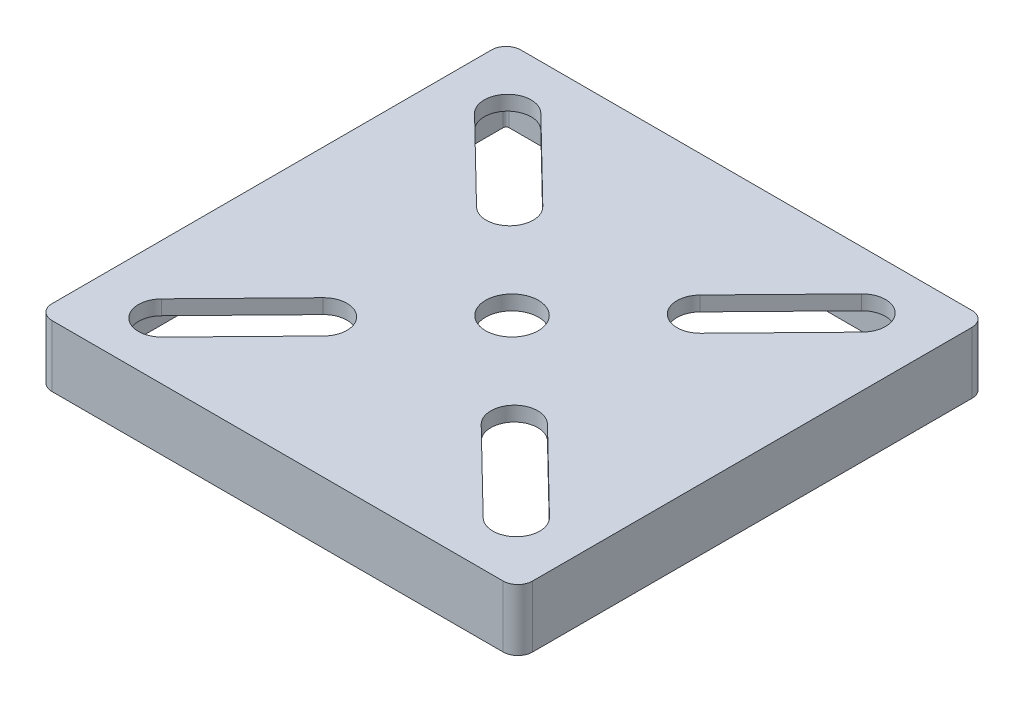
SolidWorks part; units mm, degrees
note: '?' marks a value the reader was unsure of. The reader was unsure of these and kept them because the rebuilt part matched: shared geometry of "Sketch1<4>".
ref_plane "Front Plane" through (0, 0, 0) normal (0, 0, 1) x (1, 0, 0)
ref_plane "Top Plane" through (0, 0, 0) normal (0, 1, 0) x (1, 0, 0)
ref_plane "Right Plane" through (0, 0, 0) normal (1, 0, 0) x (0, 0, -1)
sketch "Sketch1" plane through (0, 0, 0) normal (0, 1, 0) x (1, 0, 0)
  line L0 (0, 80) -> (0, -80) construction
  line L1 (-77, 80) -> (77, 80)
  line L2 (-82, 75) -> (-82, -75)
  line L3 (-77, -80) -> (77, -80)
  line L4 (82, 75) -> (82, -75)
  line L5 (-82, 80) -> (0, 0) construction
  line L6 (-54.8892, 64.727) -> (-26.9737, 37.4924)
  line L7 (-66.0624, 53.2745) -> (-38.1469, 26.0399)
  line L8 (-66.0624, 53.2745) -> (-54.8892, 64.727) construction
  line L9 (-38.1469, 26.0399) -> (-26.9737, 37.4924) construction
  line L10 (64.727, 54.8892) -> (37.4924, 26.9737)
  line L11 (53.2745, 66.0624) -> (26.0399, 38.1469)
  line L12 (54.8892, -64.727) -> (26.9737, -37.4924)
  line L13 (66.0624, -53.2745) -> (38.1469, -26.0399)
  line L14 (-64.727, -54.8892) -> (-37.4924, -26.9737)
  line L15 (-53.2745, -66.0624) -> (-26.0399, -38.1469)
  circle A0 centre (0, 0) radius 9
  arc A1 (-66.0624, 53.2745) -> (-54.8892, 64.727) centre (-60.4758, 59.0008) cw
  arc A2 (-26.9737, 37.4924) -> (-38.1469, 26.0399) centre (-32.5603, 31.7661) cw
  arc A3 (82, -75) -> (77, -80) centre (77, -75) cw
  arc A4 (-82, -75) -> (-77, -80) centre (-77, -75) ccw
  arc A5 (82, 75) -> (77, 80) centre (77, 75) ccw
  arc A6 (-82, 75) -> (-77, 80) centre (-77, 75) cw
  arc A7 (37.4924, 26.9737) -> (26.0399, 38.1469) centre (31.7661, 32.5603) cw
  arc A8 (53.2745, 66.0624) -> (64.727, 54.8892) centre (59.0008, 60.4758) cw
  arc A9 (26.9737, -37.4924) -> (38.1469, -26.0399) centre (32.5603, -31.7661) cw
  arc A10 (66.0624, -53.2745) -> (54.8892, -64.727) centre (60.4758, -59.0008) cw
  arc A11 (-37.4924, -26.9737) -> (-26.0399, -38.1469) centre (-31.7661, -32.5603) cw
  arc A12 (-53.2745, -66.0624) -> (-64.727, -54.8892) centre (-59.0008, -60.4758) cw
  point P18 (82, -80)
  point P23 (82, 80)
  point P27 (-80.5355, 78.5355)
  point P28 (-66.2021, 64.5874)
  point P53 (0, 0)
  dimension "D3" = 18
  dimension "D6" = 5
  dimension "D1" = 164
  dimension "D2" = 160
  dimension "D4" = 16
  dimension "D5" = 39
  dimension "D7" = 20
  dimension "D8" = 4
extrude "Boss-Extrude1" add sketch "Sketch1" against normal blind 21 contours A6 L2 A4 L3 A3 L4 A5 L1 A0 L6 A2 L7 A1 L11 A8 L10 A7 L13 A10 L12 A9 L15 A12 L14 A11 | A2 L6 A1 L7 | A12 L15 A11 L14 | A0 | A10 L13 A9 L12 | A8 L11 A7 L10
shell "Shell1" thickness 4 removed face at (0, -21, 0)
other "Move Face1" flip direction yes face at (0, -4, 0) parameters "D1"=1
extrude "Cut-Extrude1" cut sketch "Sketch1<4>" against normal through all contours A2 L6 A1 L7 | A12 L15 A11 L14 | A10 L13 A9 L12 | A8 L11 A7 L10 | A0
sketch "Sketch1<4>" plane through (0, 0, 0) normal (0, 1, 0) x (1, 0, 0) same geometry as "Sketch1"
sketch "Sketch2" plane through (0, -3, 0) normal (0, -1, 0) x (1, 0, 0)
  line L0 (-23.1768, 40.9402) -> (-50.4114, 68.8557)
  line L1 (-67.5902, 52.0959) -> (-40.3555, 24.1804)
  line L2 (-54.8892, -64.727) -> (-26.9737, -37.4924)
  line L3 (-38.1469, -26.0399) -> (-66.0624, -53.2745)
  line L4 (-54.8892, -64.727) -> (-26.9737, -37.4924)
  line L5 (-38.1469, -26.0399) -> (-66.0624, -53.2745)
  line L6 (-26.0399, 38.1469) -> (-53.2745, 66.0624)
  line L7 (-64.727, 54.8892) -> (-37.4924, 26.9737)
  line L8 (-26.0399, 38.1469) -> (-53.2745, 66.0624)
  line L9 (-64.727, 54.8892) -> (-37.4924, 26.9737)
  line L10 (38.1469, 26.0399) -> (66.0624, 53.2745)
  line L11 (54.8892, 64.727) -> (26.9737, 37.4924)
  line L12 (38.1469, 26.0399) -> (66.0624, 53.2745)
  line L13 (54.8892, 64.727) -> (26.9737, 37.4924)
  line L14 (26.0399, -38.1469) -> (53.2745, -66.0624)
  line L15 (64.727, -54.8892) -> (37.4924, -26.9737)
  line L16 (26.0399, -38.1469) -> (53.2745, -66.0624)
  line L17 (64.727, -54.8892) -> (37.4924, -26.9737)
  line L24 (-23.3863, 23.9709) -> (0, 0) construction
  line L25 (-21.0024, 27.2554) -> (-5.7747, 11.647)
  line L26 (-26.7286, 21.6689) -> (-11.5009, 6.0604)
  line L27 (40.9402, 23.1768) -> (68.8557, 50.4114)
  line L28 (52.0959, 67.5902) -> (24.1804, 40.3555)
  line L29 (27.2554, 21.0024) -> (11.647, 5.7747)
  line L30 (21.6689, 26.7286) -> (6.0604, 11.5009)
  line L31 (23.1768, -40.9402) -> (50.4114, -68.8557)
  line L32 (67.5902, -52.0959) -> (40.3555, -24.1804)
  line L33 (21.0024, -27.2554) -> (5.7747, -11.647)
  line L34 (26.7286, -21.6689) -> (11.5009, -6.0604)
  line L35 (-40.9402, -23.1768) -> (-68.8557, -50.4114)
  line L36 (-52.0959, -67.5902) -> (-24.1804, -40.3555)
  line L37 (-27.2554, -21.0024) -> (-11.647, -5.7747)
  line L38 (-21.6689, -26.7286) -> (-6.0604, -11.5009)
  circle A0 centre (0, 0) radius 9 construction
  circle A1 centre (0, 0) radius 9
  arc A2 (-26.9737, -37.4924) -> (-38.1469, -26.0399) centre (-32.5603, -31.7661) ccw
  arc A3 (-66.0624, -53.2745) -> (-54.8892, -64.727) centre (-60.4758, -59.0008) ccw
  arc A4 (-26.9737, -37.4924) -> (-38.1469, -26.0399) centre (-32.5603, -31.7661) ccw
  arc A5 (-66.0624, -53.2745) -> (-54.8892, -64.727) centre (-60.4758, -59.0008) ccw
  arc A6 (-53.2745, 66.0624) -> (-64.727, 54.8892) centre (-59.0008, 60.4758) ccw
  arc A7 (-37.4924, 26.9737) -> (-26.0399, 38.1469) centre (-31.7661, 32.5603) ccw
  arc A8 (-53.2745, 66.0624) -> (-64.727, 54.8892) centre (-59.0008, 60.4758) ccw
  arc A9 (-37.4924, 26.9737) -> (-26.0399, 38.1469) centre (-31.7661, 32.5603) ccw
  arc A10 (66.0624, 53.2745) -> (54.8892, 64.727) centre (60.4758, 59.0008) ccw
  arc A11 (26.9737, 37.4924) -> (38.1469, 26.0399) centre (32.5603, 31.7661) ccw
  arc A12 (66.0624, 53.2745) -> (54.8892, 64.727) centre (60.4758, 59.0008) ccw
  arc A13 (26.9737, 37.4924) -> (38.1469, 26.0399) centre (32.5603, 31.7661) ccw
  arc A14 (53.2745, -66.0624) -> (64.727, -54.8892) centre (59.0008, -60.4758) ccw
  arc A15 (37.4924, -26.9737) -> (26.0399, -38.1469) centre (31.7661, -32.5603) ccw
  arc A16 (53.2745, -66.0624) -> (64.727, -54.8892) centre (59.0008, -60.4758) ccw
  arc A17 (37.4924, -26.9737) -> (26.0399, -38.1469) centre (31.7661, -32.5603) ccw
  arc A18 (-50.4114, 68.8557) -> (-67.5902, 52.0959) centre (-59.0008, 60.4758) ccw
  arc A19 (-40.3555, 24.1804) -> (-23.1768, 40.9402) centre (-31.7661, 32.5603) ccw
  circle A26 centre (0, 0) radius 13
  arc A27 (24.1804, 40.3555) -> (40.9402, 23.1768) centre (32.5603, 31.7661) ccw
  arc A28 (68.8557, 50.4114) -> (52.0959, 67.5902) centre (60.4758, 59.0008) ccw
  arc A29 (40.3555, -24.1804) -> (23.1768, -40.9402) centre (31.7661, -32.5603) ccw
  arc A30 (50.4114, -68.8557) -> (67.5902, -52.0959) centre (59.0008, -60.4758) ccw
  arc A31 (-24.1804, -40.3555) -> (-40.9402, -23.1768) centre (-32.5603, -31.7661) ccw
  arc A32 (-68.8557, -50.4114) -> (-52.0959, -67.5902) centre (-60.4758, -59.0008) ccw
  point P73 (0, 0)
  dimension "D6" = 8
  dimension "D1" = 0
  dimension "D2" = 0
  dimension "D3" = 0
  dimension "D4" = 0
  dimension "D5" = 4
  dimension "D7" = 4
extrude "Boss-Extrude2" add sketch "Sketch2" along normal offset from surface (2 mm away) 5
ref_axis "Axis1" through (0, 0, 0) along (0, 1, 0)?
equation "\"D5@Sketch1\"=55-\"D4@Sketch1\""
